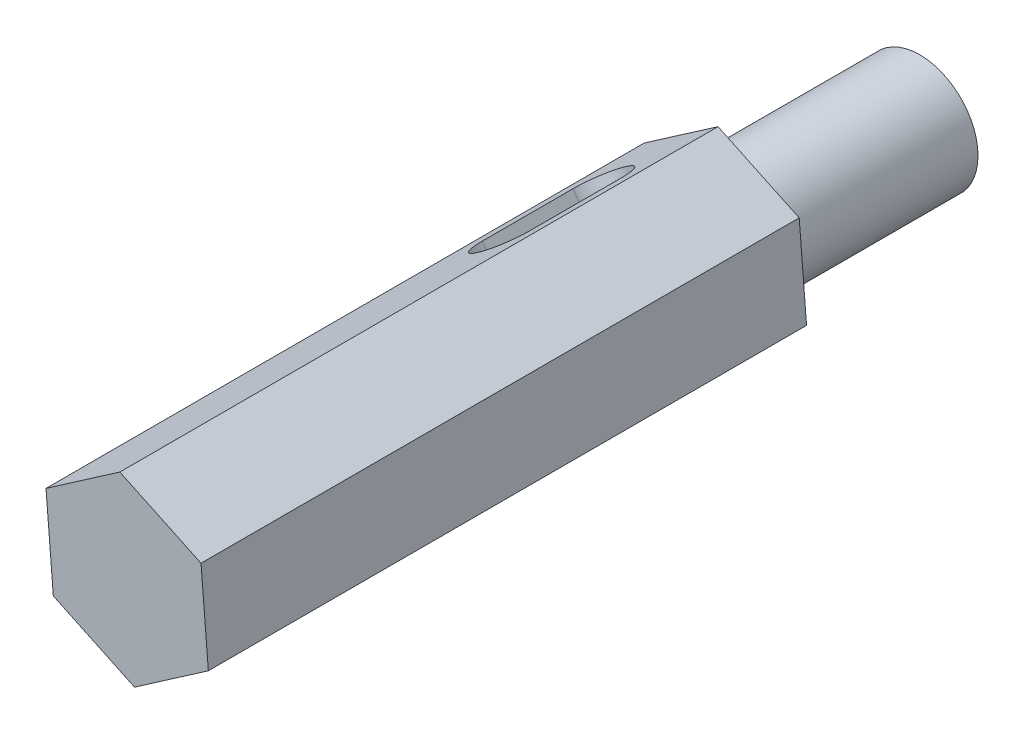
SolidWorks part; units mm, degrees
ref_plane "Front Plane" through (0, 0, 0) normal (0, 0, 1) x (1, 0, 0)
ref_plane "Top Plane" through (0, 0, 0) normal (0, 1, 0) x (1, 0, 0)
ref_plane "Right Plane" through (0, 0, 0) normal (1, 0, 0) x (0, 0, -1)
sketch "Sketch1" plane through (0, 0, 0) normal (0, 0, 1) x (1, 0, 0)
  line L1 (6.0296, 4.1722) -> (-0.5985, 7.3079)
  line L2 (-0.5985, 7.3079) -> (-6.6281, 3.1356)
  line L3 (-6.6281, 3.1356) -> (-6.0296, -4.1722)
  line L4 (-6.0296, -4.1722) -> (0.5985, -7.3079)
  line L5 (0.5985, -7.3079) -> (6.6281, -3.1356)
  line L6 (6.6281, -3.1356) -> (6.0296, 4.1722)
  circle A0 centre (0, 0) radius 6.35 construction
  circle A1 centre (0, 0) radius 2.7305
  dimension "D2" = 5.461
  dimension "D1" = 12.7
extrude "Boss-Extrude1" add sketch "Sketch1" along normal blind 20.9042
sketch "Sketch2" plane through (0, 0, 20.9042) normal (0, 0, 1) x (1, 0, 0)
  line L1 (-6.6281, 3.1356) -> (-6.0296, -4.1722)
  line L2 (-6.0296, -4.1722) -> (0.5985, -7.3079)
  line L3 (0.5985, -7.3079) -> (6.6281, -3.1356)
  line L4 (6.6281, -3.1356) -> (6.0296, 4.1722)
  line L5 (6.0296, 4.1722) -> (-0.5985, 7.3079)
  line L6 (-0.5985, 7.3079) -> (-6.6281, 3.1356)
  circle A0 centre (0, 0) radius 6.35 construction
extrude "Boss-Extrude2" add sketch "Sketch2" along normal blind 27.94
sketch "Sketch3" plane through (0, 0, 0) normal (0, 0, -1) x (-1, 0, 0)
  circle A0 centre (0, 0) radius 4.7536
  circle A1 centre (0, 0) radius 2.7305
  dimension "D1" = 9.5072
  dimension "D2" = 5.461
extrude "Boss-Extrude3" add sketch "Sketch3" along normal blind 15.875
sketch "Sketch4" plane through (-3.6133, 5.2218, 0) normal (-0.569, 0.8223, 0) x (0.8223, 0.569, 0)
  line L0 (0, -14.2748) -> (0, -6.858) construction
  line L1 (-2.3876, -14.2748) -> (-2.3876, -6.858)
  line L2 (2.3876, -14.2748) -> (2.3876, -6.858)
  line L4 (3.6662, 0) -> (-3.6662, 0) construction
  line L5 (3.6662, -48.8442) -> (-3.6662, -48.8442) construction
  arc A0 (-2.3876, -14.2748) -> (2.3876, -14.2748) centre (0, -14.2748) ccw
  arc A1 (2.3876, -6.858) -> (-2.3876, -6.858) centre (0, -6.858) ccw
  point P3 (0, -10.5664)
  dimension "D1" = 2.3876
  dimension "D2" = 34.5694
  dimension "D3" = 6.858
extrude "Cut-Extrude1" cut sketch "Sketch4" against normal up to surface (12.7 mm away) up to face at (3.6133, -5.2218, 24.4221)
